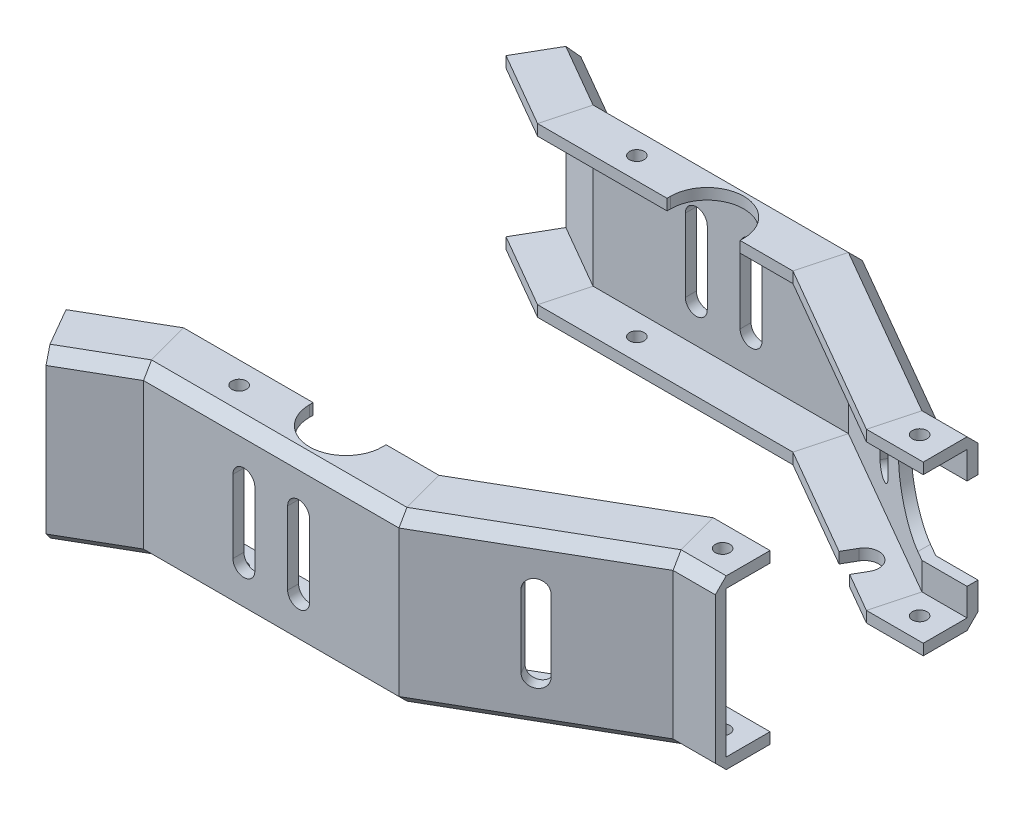
SolidWorks part; units mm, degrees
material "ABS PC"
ref_plane "Front Plane" through (0, 0, 0) normal (0, 0, 1) x (1, 0, 0)
ref_plane "Top Plane" through (0, 0, 0) normal (0, 1, 0) x (1, 0, 0)
ref_plane "Right Plane" through (0, 0, 0) normal (1, 0, 0) x (0, 0, -1)
sketch "Sketch6" plane through (0, 0, 0) normal (0, 1, 0) x (1, 0, 0)
  line L0 (0, 0) -> (-70, 0)
  line L1 (-70, 0) -> (-87.3205, -10)
  line L2 (0, 0) -> (47.6314, 27.5)
  line L3 (47.6314, 27.5) -> (59.6314, 27.5)
  dimension "D1" = 70
  dimension "D2" = 20
  dimension "D3" = 150
  dimension "D4" = 55
  dimension "D5" = 12
ref_plane "Plane5" through (0, 0, 0) normal (1, 0, 0) x (0, 0, -1)
sketch "Sketch7" plane through (0, 0, 0) normal (1, 0, 0) x (0, 0, -1)
  line L0 (1.3953, 0) -> (11.0315, 0) construction
  line L2 (-1.6047, -23) -> (-1.6047, 23)
  line L4 (1.3953, -20) -> (1.3953, 20)
  line L5 (-1.6047, -23) -> (1.3953, 20) construction
  line L6 (-1.6047, 23) -> (1.3953, -20) construction
  line L7 (13.3953, 20) -> (13.3953, 23)
  line L8 (1.3953, -20) -> (13.3953, -20)
  line L10 (-1.6047, -23) -> (13.3953, -23)
  line L11 (13.3953, -20) -> (13.3953, -23)
  line L12 (-1.6047, 23) -> (13.3953, 23)
  line L14 (1.3953, 20) -> (13.3953, 20)
  point P0 (0, 0)
  dimension "D1" = 3
  dimension "D3" = 3
  dimension "D2" = 40
  dimension "D5" = 15
sweep "Sweep8" add profiles "Sketch7" path "Sketch6"
ref_plane "Plane6" through (0, 0, -61.8953) normal (0, 0, -1) x (-1, 0, 0)
sketch "Sketch8" plane through (0, 23, 0) normal (0, 1, 0) x (1, 0, 0)
  line L1 (-73.5893, 13.3953) -> (-94.0182, 1.6007) construction
  line L3 (-89.0182, -7.0595) -> (-94.0182, 1.6007)
  line L4 (-94.0182, 1.6007) -> (-81.0278, 9.1007)
  line L5 (-94.0182, 1.6007) -> (-86.5182, -11.3897) construction
  line L6 (-81.0278, 9.1007) -> (-89.0182, -7.0595)
  dimension "D1" = 15
  dimension "D2" = 10
extrude "Cut-Extrude1" [suppressed] cut sketch "Sketch8" against normal through all
sketch "Sketch9" plane through (0, 23, 0) normal (0, 1, 0) x (1, 0, 0)
  line L0 (-73.5893, 13.3953) -> (-94.0182, 1.6007) construction
  line L1 (-94.0182, 1.6007) -> (-86.5182, -11.3897) construction
  line L2 (-83.6259, 7.6007) -> (-94.0182, 1.6007)
  line L3 (-94.0182, 1.6007) -> (-89.5182, -6.1935)
  line L4 (-89.5182, -6.1935) -> (-86.9201, -4.6935)
  line L5 (-83.6259, 7.6007) -> (-79.1259, -0.1935) construction
  line L6 (-79.1259, -0.1935) -> (-86.9201, -4.6935) construction
  arc A1 (-83.6259, 7.6007) -> (-86.9201, -4.6935) centre (-91.4201, 3.1007) cw
  dimension "D1" = 12
  dimension "D2" = 9
extrude "Cut-Extrude2" [suppressed] cut sketch "Sketch9" against normal through all
sketch "Sketch10" plane through (0, 23, 0) normal (0, 1, 0) x (1, 0, 0)
  line L0 (-3.5893, 13.3953) -> (-73.5893, 13.3953) construction
  line L1 (-38.0893, 13.3953) -> (-18.0893, 13.3953)
  line L2 (-38.0893, 13.3953) -> (-38.0893, 12.3953)
  line L3 (-38.0893, 12.3953) -> (-18.0893, 12.3953) construction
  line L4 (-18.0893, 13.3953) -> (-18.0893, 12.3953)
  arc A0 (-38.0893, 12.3953) -> (-18.0893, 12.3953) centre (-28.0893, 12.3953) ccw
  dimension "D1" = 1
  dimension "D2" = 20
  dimension "D3" = 24.5
extrude "Cut-Extrude3" cut sketch "Sketch10" against normal blind 5
sketch "Sketch11" plane through (0, 0, 1.6047) normal (0, 0, 1) x (1, 0, 0)
  line L0 (-34.57, 23) -> (-34.57, -23) construction
  line L3 (-42.07, -10) -> (-42.07, 10) construction
  line L4 (-45.07, -10) -> (-45.07, 10)
  line L5 (-39.07, -10) -> (-39.07, 10)
  line L6 (-27.07, -10) -> (-27.07, 10) construction
  line L7 (-24.07, -10) -> (-24.07, 10)
  line L8 (-30.07, -10) -> (-30.07, 10)
  line L9 (-34.57, 0) -> (-42.07, 0) construction
  line L10 (0.43, 23) -> (-69.57, 23) construction
  line L11 (0.43, -23) -> (-69.57, -23) construction
  arc A0 (-45.07, -10) -> (-39.07, -10) centre (-42.07, -10) ccw
  arc A1 (-39.07, 10) -> (-45.07, 10) centre (-42.07, 10) ccw
  arc A2 (-24.07, -10) -> (-30.07, -10) centre (-27.07, -10) cw
  arc A3 (-30.07, 10) -> (-24.07, 10) centre (-27.07, 10) cw
  point P8 (-42.07, 0)
  point P15 (-27.07, 0)
  dimension "D1" = 15
  dimension "D2" = 6
  dimension "D3" = 20
extrude "Cut-Extrude4" cut sketch "Sketch11" against normal blind 10
chamfer "Chamfer1" distance 3 angle 45 8 edges at (-78.0441, -23, 6.4972) (-34.57, -23, 1.6047) (24.2457, -23, -12.1453) (-78.0441, 23, 6.4972) (-34.57, 23, 1.6047) (24.2457, 23, -12.1453) (53.8464, -23, -25.8953) (53.8464, 23, -25.8953)
sketch "Sketch14" plane through (0.8023, 0, 1.3897) normal (0.5, 0, 0.866) x (0.866, 0, -0.5)
  line L0 (27.07, -10) -> (27.07, 10) construction
  line L1 (24.07, -10) -> (24.07, 10)
  line L2 (30.07, -10) -> (30.07, 10)
  line L3 (27.07, -20) -> (27.07, -10) construction
  line L5 (0, 0) -> (27.07, 0) construction
  line L6 (-0.43, -20) -> (54.57, -20) construction
  arc A0 (24.07, -10) -> (30.07, -10) centre (27.07, -10) ccw
  arc A1 (30.07, 10) -> (24.07, 10) centre (27.07, 10) ccw
  point P2 (27.07, 0)
  dimension "D1" = 20
  dimension "D2" = 6
extrude "Cut-Extrude6" cut sketch "Sketch14" against normal blind 3
hole_wizard "Ø4.0mm Dowel Hole2" positions "Sketch18" profile "Sketch19" hole size "Ø4.0" standard "ANSI Metric" end condition through all
sketch "Sketch18" plane through (0, -23, 0) normal (0, -1, 0) x (-1, 0, 0)
  line L6 (-52.6314, 34.8953) -> (-52.6314, 28.8953) construction
  line L7 (-59.6314, 28.8953) -> (-47.2575, 28.8953) construction
  line L11 (52.3686, 7.3953) -> (52.3686, 1.3953) construction
  line L12 (0.3739, 1.3953) -> (70.3739, 1.3953) construction
  line L14 (-59.6314, 28.8953) -> (-59.6314, 40.8953) construction
  point P0 (52.3686, 7.3953)
  point P2 (-52.6314, 34.8953)
  dimension "D1" = 6
  dimension "D2" = 105
  dimension "D3" = 7
sketch "Sketch19" plane through (-52.3686, -23, -7.3953) normal (1, 0, 0) x (0, 0, -1)
  line L0 (0, 0) -> (0, 46)
  line L1 (0, 46) -> (2, 46)
  line L2 (2, 46) -> (2, 0)
  line L5 (2, 0) -> (0, 0)
  line L11 (0, -6.35) -> (0, 107.95) construction
  dimension "Thru Hole Dia." = 4
  dimension "Thru Hole Depth" = 46
sketch "Sketch22" plane through (0, -23, 0) normal (0, -1, 0) x (1, 0, 0)
  line L0 (26.2886, -30.6453) -> (33.2168, -34.6453)
  line L1 (26.2886, -30.6453) -> (28.2886, -27.1812)
  line L2 (33.2168, -34.6453) -> (35.2168, -31.1812)
  line L3 (28.2886, -27.1812) -> (35.2168, -31.1812)
  line L4 (44.0421, -40.8953) -> (-3.5893, -13.3953) construction
  arc A0 (28.2886, -27.1812) -> (35.2168, -31.1812) centre (31.7527, -29.1812) cw
  line M7 (-3.5893, -13.3953) -> (44.0421, -40.8953)
  dimension "D1" = 4
  dimension "D2" = 8
  dimension "D3" = 12.5
extrude "Cut-Extrude9" cut sketch "Sketch22" against normal blind 10 contours A0 L3 | L3 L1 L2 M7 region at (30.7527, -23, -30.9133) region at (32.6015, -23, -27.711)
mirror "Mirror2" about plane through (0, 0, -61.8953) normal (0, 0, -1) of bodies 116 103
sketch "Sketch20" plane through (0, 0, -97.8953) normal (0, 0, -1) x (-1, 0, 0)
  line L0 (-59.6314, 0) -> (-52.1314, 0) construction
  line L1 (-59.6314, 20) -> (-59.6314, -20) construction
  line L3 (-44.6314, -12.5) -> (-59.6314, -12.5)
  line L4 (-44.6314, -12.5) -> (-44.6314, 12.5)
  line L5 (-44.6314, 12.5) -> (-59.6314, 12.5)
  line L6 (-59.6314, -12.5) -> (-59.6314, 12.5)
  line L7 (-44.6314, -12.5) -> (-59.6314, 12.5) construction
  line L8 (-44.6314, 12.5) -> (-59.6314, -12.5) construction
  arc A0 (-44.6314, 12.5) -> (-44.6314, -12.5) centre (-44.6314, 0) cw
  point P5 (-52.1314, 0)
  line M3 (-48.0614, -20) -> (-48.0614, 20)
  line M5 (-59.6314, 20) -> (-59.6314, -20)
  dimension "D1" = 25
  dimension "D2" = 15
extrude "Cut-Extrude7" cut sketch "Sketch20" against normal blind 5 and the other way through all contours A0 L4 | L5 L3 M3 M5 | L4 L5 L3 M3 region at (46.3464, 0, -97.8953) region at (39.3262, 0, -97.8953) region at (53.8464, 0, -97.8953)
sketch "Sketch21" plane through (0, 0, -25.8953) normal (0, 0, 1) x (1, 0, 0)
  line L0 (59.6314, 0) -> (54.6314, 0) construction
  line L2 (59.6314, 20) -> (59.6314, -20) construction
  line L3 (59.6314, -7.5) -> (49.6314, -7.5)
  line L4 (59.6314, -7.5) -> (59.6314, 7.5)
  line L5 (59.6314, 7.5) -> (49.6314, 7.5)
  line L6 (49.6314, -7.5) -> (49.6314, 7.5)
  line L7 (59.6314, -7.5) -> (49.6314, 7.5) construction
  line L8 (59.6314, 7.5) -> (49.6314, -7.5) construction
  arc A0 (49.6314, 7.5) -> (49.6314, -7.5) centre (49.6314, 0) ccw
  point P5 (54.6314, 0)
  line M14 (48.0614, 20) -> (48.0614, -20)
  line M16 (59.6314, -20) -> (59.6314, 20)
  dimension "D1" = 15
  dimension "D2" = 10
extrude "Cut-Extrude8" [suppressed] cut sketch "Sketch21" against normal blind 10 and the other way blind 10 contours A0 M14 | L6 A0 M14 | L6 L3 L5 M16
